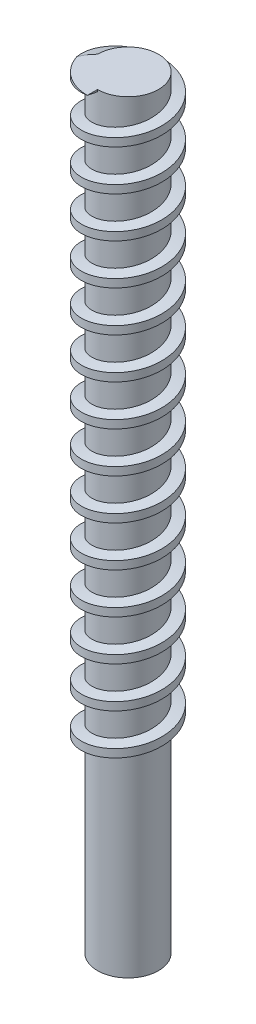
SolidWorks part; units mm, degrees
material "Stainless Steel (ferritic)"
ref_plane "Front Plane" through (0, 0, 0) normal (0, 0, 1) x (1, 0, 0)
ref_plane "Top Plane" through (0, 0, 0) normal (0, 1, 0) x (1, 0, 0)
ref_plane "Right Plane" through (0, 0, 0) normal (1, 0, 0) x (0, 0, -1)
sketch "Sketch1" plane through (0, 0, 0) normal (0, 1, 0) x (1, 0, 0)
  circle A0 centre (0, 0) radius 3
  dimension "D1" = 6
extrude "Boss-Extrude1" add sketch "Sketch1" along normal blind 85
sketch "Sketch2" plane through (0, 85, 0) normal (0, 1, 0) x (1, 0, 0)
  circle A0 centre (0, 0) radius 3
sketch "Sketch3" plane through (0, 0, 0) normal (0, 0, 1) x (1, 0, 0)
  line L0 (-3, 85) -> (-4, 84.8)
  line L1 (-4, 84.8) -> (-4, 84)
  line L2 (-4, 84) -> (-3, 83.8)
  line L3 (-3, 85) -> (-3, 0) construction
  line L4 (-3, 83.8) -> (-3, 85)
  dimension "D1" = 0.8
  dimension "D2" = 1.2
  dimension "D3" = 1
  dimension "D4" = 0.2
curve "Helix/Spiral2" pitch 4 height 57 radius 3 centre (0, 85, 0) axis (0, -1, 0) start towards (0, 0, 1)
sweep "Sweep2" add profiles "Sketch3" path "Helix/Spiral2"
sketch "Sketch5" plane through (0, 0, 0) normal (0, -1, 0) x (1, 0, 0)
  circle A0 centre (0, 0) radius 4.9187
sketch "Sketch7" plane through (0, 85, 0) normal (0, 1, 0) x (1, 0, 0)
  circle A0 centre (0, 0) radius 4.7584
extrude "Cut-Extrude6" cut sketch "Sketch7" along normal blind 7
extrude "Cut-Extrude7" cut sketch "Sketch5" against normal blind 10
sketch "Sketch9" plane through (0, 0, 0) normal (1, 0, 0) x (0, 0, -1)
  line L0 (3, 0) -> (-3, 0) construction
  line L1 (3, 0) -> (-3, 0) construction
  line L2 (0, 0) -> (0, 59.9001) construction
  line L3 (3, 85) -> (-3, 85) construction
  line L4 (3, 85) -> (-3, 85) construction
